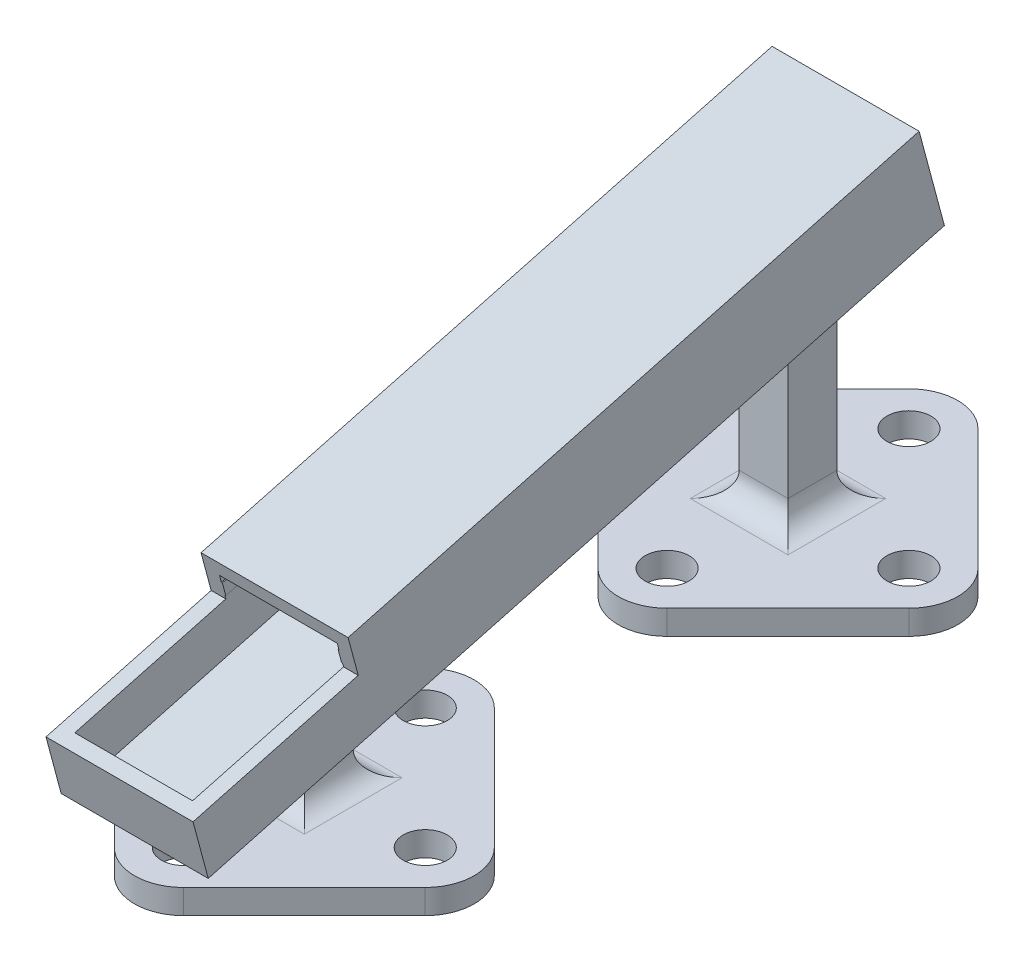
SolidWorks part; units mm, degrees
ref_plane "Front" through (0, 0, 0) normal (0, 0, 1) x (1, 0, 0)
ref_plane "Top" through (0, 0, 0) normal (0, 1, 0) x (1, 0, 0)
ref_plane "Right" through (0, 0, 0) normal (1, 0, 0) x (0, 0, -1)
ref_axis "Axis1" through (0, 55, 0) along (0, -1, 0)
ref_axis "Axis2" through (88.99, 0, 0) along (-1, 0, 0)
ref_axis "Axis3" through (0, 0, 55) along (0, 0, -1)
sketch "Sketch1" plane through (0, 0, 0) normal (0, 1, 0) x (1, 0, 0)
  line L0 (-24.75, 0) -> (0, 24.75) construction
  line L9 (-24.75, 0) -> (0, -24.75) construction
  line L11 (0, 24.75) -> (24.75, 0) construction
  line L12 (0, -24.75) -> (24.75, 0) construction
  line L13 (-24.75, 0) -> (24.75, 0) construction
  line L14 (0, 24.75) -> (0, -24.75) construction
  line L15 (-31.8211, 7.0711) -> (-7.0711, 31.8211)
  line L16 (7.0711, 31.8211) -> (31.8211, 7.0711)
  line L17 (7.0711, -31.8211) -> (31.8211, -7.0711)
  line L18 (-31.8211, -7.0711) -> (-7.0711, -31.8211)
  line L19 (0, -38.8921) -> (38.8921, 0) construction
  line L20 (-38.8921, 0) -> (0, -38.8921) construction
  line L21 (0, 38.8921) -> (38.8921, 0) construction
  line L22 (-38.8921, 0) -> (0, 38.8921) construction
  arc A4 (7.0711, -31.8211) -> (-7.0711, -31.8211) centre (0, -24.75) cw
  arc A5 (31.8211, 7.0711) -> (31.8211, -7.0711) centre (24.75, 0) cw
  arc A6 (-7.0711, 31.8211) -> (7.0711, 31.8211) centre (0, 24.75) cw
  arc A7 (-31.8211, 7.0711) -> (-31.8211, -7.0711) centre (-24.75, 0) ccw
  circle A8 centre (0, 24.75) radius 4.5
  circle A9 centre (24.75, 0) radius 4.5
  circle A10 centre (0, -24.75) radius 4.5
  circle A11 centre (-24.75, 0) radius 4.5
  point P1 (0, 0)
  dimension "D3" = 10
  dimension "D4" = 9
  dimension "D1" = 49.5
  dimension "D2" = 10
extrude "Boss-Extrude1" add sketch "Sketch1" along normal mid plane 5
ref_plane "Plane1" through (0, 0, 49.5) normal (0, 0, 1) x (1, 0, 0)
mirror "Mirror3" about plane through (0, 0, 49.5) normal (0, 0, 1) of bodies 101
sketch "Sketch2" plane through (0, 0, 0) normal (1, 0, 0) x (0, 0, -1)
  line L0 (-106.0711, 2.5) -> (-130.8211, 2.5) construction
  line L1 (-104, 2.5) -> (-94, 2.5)
  line L2 (-104, 2.5) -> (-104, 47.5)
  line L3 (-104, 47.5) -> (-94, 47.5)
  line L4 (-94, 2.5) -> (-94, 47.5)
  line L5 (-106.0711, -2.5) -> (-91.9289, -2.5) construction
  line L6 (-67.1789, -2.5) -> (-91.9289, -2.5) construction
  point P8 (-99, -2.5)
  point P9 (-99, 47.5)
  dimension "D1" = 10
  dimension "D2" = 50
extrude "Boss-Extrude2" add sketch "Sketch2" along normal mid plane 10 separate body
mirror "Mirror5" about plane through (0, 0, 49.5) normal (0, 0, 1) of bodies 103
sketch "Sketch3" plane through (0, 0, 0) normal (1, 0, 0) x (0, 0, -1)
  line L0 (-104, 17.5) -> (5, 46.7065)
  line L1 (-67.1789, -2.5) -> (-91.9289, -2.5) construction
  line L2 (-104, 47.5) -> (-104, 2.5) construction
  line L3 (-106.0711, 2.5) -> (-130.8211, 2.5) construction
  line L4 (5, 47.5) -> (5, 2.5) construction
  point P6 (-104, 17.5)
  dimension "D1" = 15
  dimension "D2" = 15
extrude "Cut-Extrude1" cut sketch "Sketch3" against normal through all both and the other way through all
sketch "Sketch4" plane through (0, 0, 0) normal (1, 0, 0) x (0, 0, -1)
  line L0 (-130.8211, 10.3133) -> (14.0678, 49.1362)
  line L1 (-130.8211, 10.3133) -> (-131.3387, 12.2452)
  line L2 (14.0678, 49.1362) -> (13.5502, 51.068)
  line L3 (-131.3387, 12.2452) -> (13.5502, 51.068)
  line L6 (-104, 17.5) -> (-94, 20.1795) construction
  dimension "D1" = 2
  dimension "D2" = 150
extrude "Boss-Extrude3" add sketch "Sketch4" along normal mid plane 24.1 separate body
combine bodies "Combine1" operation type add bodies to combine 102 106
combine bodies "Combine2" operation type add bodies to combine 107 101
fillet "Fillet1" radius 5 4 edges at (0, 2.5, 94) (-5, 2.5, 99) (0, 2.5, 104) (5, 2.5, 99)
fillet "Fillet2" radius 5 4 edges at (0, 2.5, 5) (0, 2.5, -5) (-5, 2.5, 0) (5, 2.5, 0)
sketch "Sketch5" plane through (0, 44.2596, 11.8593) normal (0, 0.9659, 0.2588) x (1, 0, 0)
  line L0 (12.05, -111.6442) -> (0, -111.6442) construction
  line L1 (12.05, 26.3058) -> (12.05, -123.6942) construction
  line L2 (0, -111.6442) -> (0, -123.6942) construction
  line L3 (12.05, -123.6942) -> (-12.05, -123.6942) construction
  line L4 (-11.83, -111.6442) -> (-12.05, -123.6942)
  line L5 (-12.05, -123.6942) -> (0, -123.6942)
  line L6 (0, -123.6942) -> (12.05, -123.6942)
  line L7 (12.05, -123.6942) -> (12.05, -111.6442)
  circle A0 centre (0, -111.6442) radius 8.73 construction
  circle A1 centre (0, -111.6442) radius 8.83
  circle A2 centre (0, -111.6442) radius 11.83
  dimension "D1" = 17.46
  dimension "D2" = 0.1
  dimension "D3" = 3
sketch "Sketch6" plane through (0, 44.2596, 11.8593) normal (0, 0.9659, 0.2588) x (1, 0, 0)
  line L4 (-12.05, 26.3058) -> (-12.05, -123.6942)
  line L5 (-12.05, -123.6942) -> (12.05, -123.6942)
  line L6 (12.05, -123.6942) -> (12.05, 26.3058)
  line L7 (12.05, 26.3058) -> (-12.05, 26.3058)
  line L8 (-12.05, 26.3058) -> (-12.05, -123.6942)
  line L9 (-12.05, -123.6942) -> (12.05, -123.6942)
  line L10 (12.05, -123.6942) -> (12.05, 26.3058)
  line L11 (12.05, 26.3058) -> (-12.05, 26.3058)
  line L16 (-15.05, 29.3058) -> (-15.05, -126.6942)
  line L17 (-15.05, -126.6942) -> (15.05, -126.6942)
  line L18 (15.05, -126.6942) -> (15.05, 29.3058)
  line L19 (15.05, 29.3058) -> (-15.05, 29.3058)
  line L20 (-15.05, 29.3058) -> (-15.05, -126.6942)
  line L21 (-15.05, -126.6942) -> (15.05, -126.6942)
  line L22 (15.05, -126.6942) -> (15.05, 29.3058)
  line L23 (15.05, 29.3058) -> (-15.05, 29.3058)
  dimension "D1" = 0
  dimension "D2" = 3
extrude "Boss-Extrude4" add sketch "Sketch6" against normal up to vertex (2 mm away) and the other way blind 10 up to point (12.05, 49.1362, -14.0678)
sketch "Sketch7" plane through (0, 53.9188, 14.4475) normal (0, 0.9659, 0.2588) x (1, 0, 0)
  line L0 (12.05, 26.3058) -> (12.05, -123.6942) construction
  line L1 (12.05, 26.3058) -> (12.05, -91.6942)
  line L3 (-12.05, 26.3058) -> (-12.05, -123.6942) construction
  line L4 (15.05, 29.3058) -> (-15.05, 29.3058)
  line L5 (-15.05, 29.3058) -> (-15.05, -126.6942)
  line L6 (-15.05, -126.6942) -> (15.05, -126.6942)
  line L7 (15.05, -126.6942) -> (15.05, 29.3058)
  line L8 (15.05, 29.3058) -> (-15.05, 29.3058)
  line L9 (-15.05, 29.3058) -> (-15.05, -91.6942)
  line L11 (15.05, -91.6942) -> (15.05, 29.3058)
  line L12 (12.05, 26.3058) -> (-12.05, 26.3058) construction
  line L14 (-12.05, 26.3058) -> (-12.05, -91.6942)
  line L15 (12.05, 26.3058) -> (-12.05, 26.3058)
  line L16 (15.05, -91.6942) -> (12.05, -91.6942)
  line L17 (-12.05, -91.6942) -> (-15.05, -91.6942)
  line L18 (-15.05, -126.6942) -> (15.05, -126.6942) construction
  dimension "D2" = 35
  dimension "D1" = 0
extrude "Boss-Extrude5" add sketch "Sketch7" along normal blind 5
sketch "Sketch8" plane through (0, 58.7485, 15.7416) normal (0, 0.9659, 0.2588) x (1, 0, 0)
  line L0 (-15.05, 29.3058) -> (-15.05, -91.6942) construction
  line L1 (-15.05, -91.6942) -> (15.05, -91.6942)
  line L2 (-15.05, -91.6942) -> (-15.05, 29.3058)
  line L3 (-15.05, 29.3058) -> (15.05, 29.3058)
  line L4 (15.05, -91.6942) -> (15.05, 29.3058)
extrude "Boss-Extrude6" add sketch "Sketch8" along normal blind 3
sketch "Sketch10" plane through (0, 6.8085, -25.4095) normal (0, -0.2588, 0.9659) x (1, 0, 0)
  line L4 (-12.05, 45.8209) -> (12.05, 45.8209)
  line L5 (12.05, 45.8209) -> (12.05, 60.8209)
  line L6 (12.05, 60.8209) -> (-12.05, 60.8209)
  line L7 (-12.05, 60.8209) -> (-12.05, 45.8209)
  line L8 (-12.05, 45.8209) -> (12.05, 45.8209)
  line L9 (12.05, 45.8209) -> (12.05, 60.8209)
  line L10 (12.05, 60.8209) -> (-12.05, 60.8209)
  line L11 (-12.05, 60.8209) -> (-12.05, 45.8209)
  dimension "D1" = 0
extrude "Cut-Extrude2" cut sketch "Sketch10" against normal up to next
sketch "Sketch11" plane through (0, 7.5849, -28.3073) normal (0, 0.2588, -0.9659) x (-1, 0, 0)
  line L0 (-12.05, 56.6209) -> (-11.85, 56.6209)
  line L1 (-12.05, 45.8209) -> (12.05, 45.8209) construction
  line L2 (-11.85, 56.6209) -> (-11.85, 59.3209)
  line L3 (-11.85, 59.3209) -> (-12.05, 59.3209)
  line L4 (-12.05, 60.8209) -> (-12.05, 45.8209) construction
  line L5 (-12.05, 59.3209) -> (-12.05, 56.6209)
  line L6 (0, 43.8209) -> (0, 45.8209) construction
  line L7 (-15.05, 43.8209) -> (15.05, 43.8209) construction
  line L8 (12.05, 59.3209) -> (12.05, 56.6209)
  line L9 (11.85, 59.3209) -> (12.05, 59.3209)
  line L10 (11.85, 56.6209) -> (11.85, 59.3209)
  line L11 (12.05, 56.6209) -> (11.85, 56.6209)
  dimension "D1" = 0.2
  dimension "D2" = 2.7
  dimension "D3" = 13.5
extrude "Boss-Extrude7" add sketch "Sketch11" against normal up to surface (121 mm away) up to face at (0, 33.3259, 103.8584)
